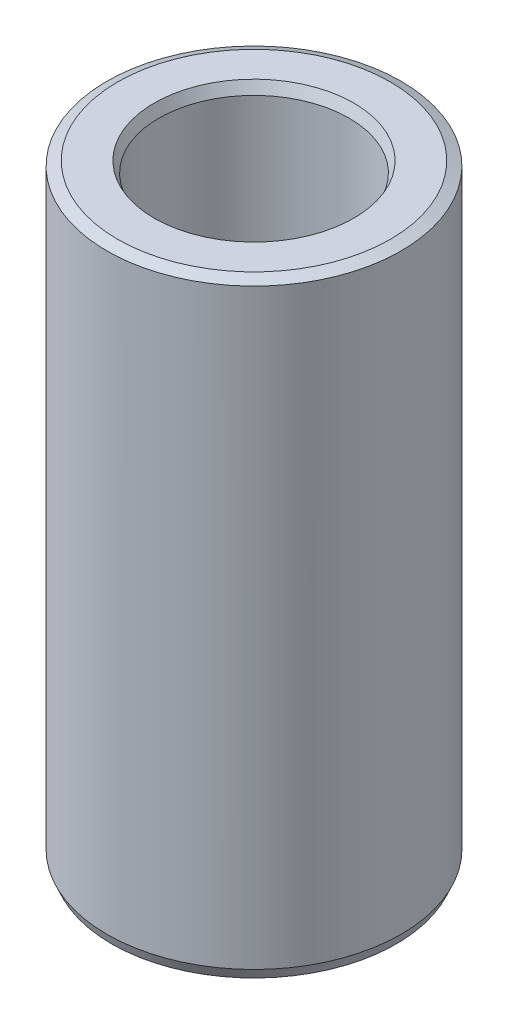
SolidWorks part; units mm, degrees
ref_plane "Front Plane" through (0, 0, 0) normal (0, 0, 1) x (1, 0, 0)
ref_plane "Top Plane" through (0, 0, 0) normal (0, 1, 0) x (1, 0, 0)
ref_plane "Right Plane" through (0, 0, 0) normal (1, 0, 0) x (0, 0, -1)
sketch "Sketch1" plane through (0, 0, 0) normal (0, 1, 0) x (1, 0, 0)
  circle A0 centre (0, 0) radius 30
  dimension "SLEEVE_OD" = 60
extrude "Boss-Extrude1" add sketch "Sketch1" along normal blind 123.8853
sketch "Sketch2" plane through (0, 0, 0) normal (0, 1, 0) x (1, 0, 0)
  circle A0 centre (0, 0) radius 19.3984
  dimension "BORE_D" = 38.7968
extrude "Cut-Extrude1" cut sketch "Sketch2" along normal through all
chamfer "Chamfer1" distance 0.9613 angle 66.268 4 edges at (0, 123.8853, 19.3984) (0, 0, 19.3984) (0, 0, 30) (0, 123.8853, 30) first distance on face at (0, 123.8853, 19.3984) first distance on face at (0, 0, 19.3984) first distance on face at (0, 123.8853, 30)
